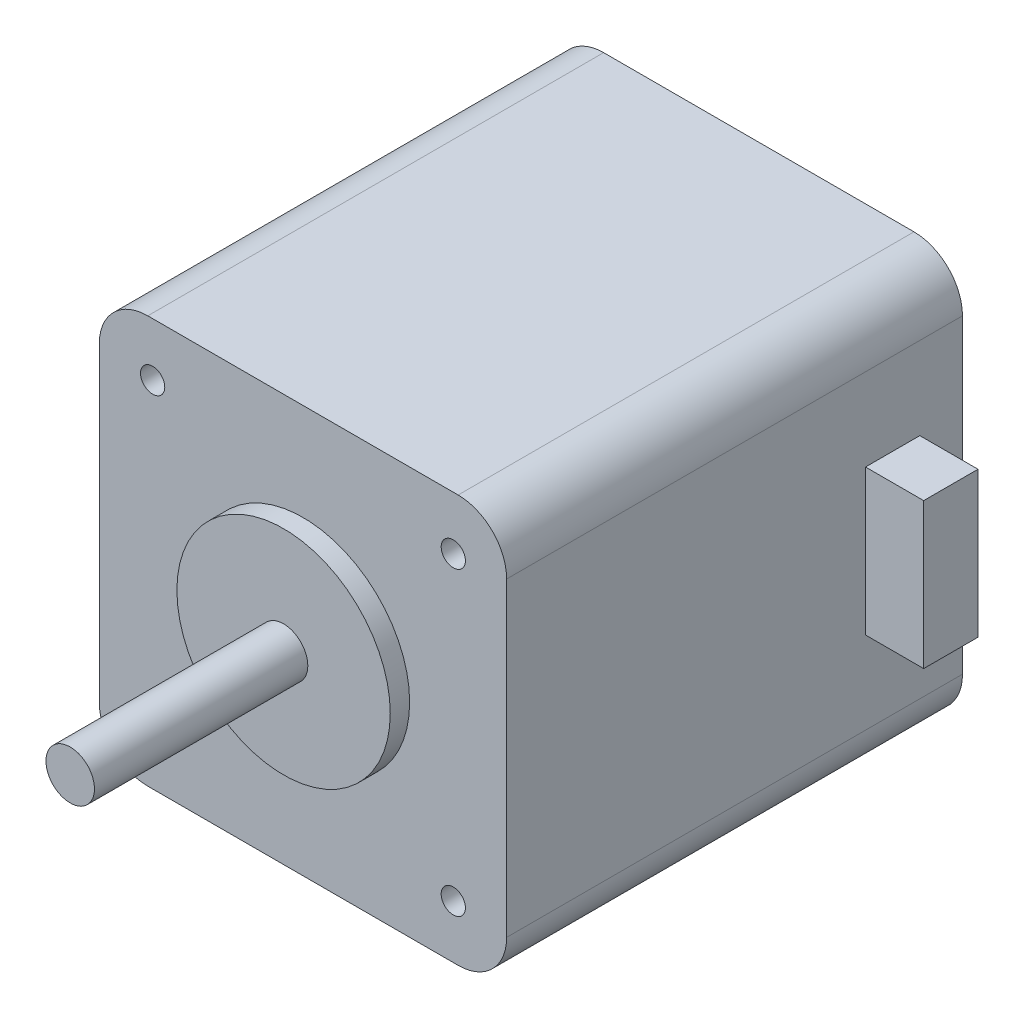
SolidWorks part; units mm, degrees
ref_plane "Front Plane" through (0, 0, 0) normal (0, 0, 1) x (1, 0, 0)
ref_plane "Top Plane" through (0, 0, 0) normal (0, 1, 0) x (1, 0, 0)
ref_plane "Right Plane" through (0, 0, 0) normal (1, 0, 0) x (0, 0, -1)
sketch "Sketch1" plane through (0, 0, 0) normal (0, 0, 1) x (1, 0, 0)
  line L1 (-21, 21) -> (21, 21)
  line L2 (-21, 21) -> (-21, -21)
  line L3 (-21, -21) -> (21, -21)
  line L4 (21, 21) -> (21, -21)
  line L5 (-21, 21) -> (21, -21) construction
  line L6 (-21, -21) -> (21, 21) construction
  point P0 (0, 0)
  dimension "D1" = 42
extrude "Boss-Extrude1" add sketch "Sketch1" along normal blind 47 contours L2 L1 L4 L3
sketch "Sketch2" plane through (0, 0, 47) normal (0, 0, 1) x (1, 0, 0)
  circle A0 centre (0, 0) radius 11
  circle A1 centre (0, 0) radius 2.5
  dimension "D1" = 22
  dimension "D2" = 5
extrude "Boss-Extrude4" add sketch "Sketch2" along normal blind 24 contours A1
extrude "Boss-Extrude5" add sketch "Sketch2<5>" along normal blind 2
sketch "Sketch2<5>" plane through (0, 0, 47) normal (0, 0, 1) x (1, 0, 0) same geometry as "Sketch2"
hole_wizard "M3 Tapped Hole3" positions "3DSketch4" profile "Sketch12" tap size "M3" standard "ISO"
sketch3d "3DSketch4"
  line L0 (-21, 21, 47) -> (-21, -21, 47) construction
  line L1 (-21, 21, 47) -> (21, 21, 47) construction
  point P0 (-15.5, 15.5, 47)
  dimension "D1" = 5.5
  dimension "D2" = 5.5
sketch "Sketch12" plane through (-15.5, 15.5, 47) normal (1, 0, 0) x (0, -1, 0)
  line L0 (0, 0) -> (0, 6.7511)
  line L1 (0, 6.7511) -> (1.25, 6)
  line L2 (1.25, 6) -> (1.25, 0)
  line L5 (1.25, 0) -> (0, 0)
  line L10 (0, 6.7511) -> (-1.25, 6) construction
  line L11 (0, -6.35) -> (0, 107.95) construction
  dimension "Tap Drill Dia." = 2.5
  dimension "Tap Drill Depth" = 6
  dimension "Drill Angle" = 118
cosmetic thread "Hole Thread9" parameters "D1"=4.5, "D2"=3
pattern_circular "CirPattern1" count 4 every 90 about axis through (0, 0, 49) along (0, 0, 1) of "M3 Tapped Hole3"
cosmetic thread "Hole Thread10" parameters "D1"=4.5, "D2"=3
cosmetic thread "Hole Thread11" parameters "D1"=4.5, "D2"=3
cosmetic thread "Hole Thread12" parameters "D1"=4.5, "D2"=3
fillet "Fillet1" radius 5 4 edges at (-21, -21, 23.5) (-21, 21, 23.5) (21, -21, 23.5) (21, 21, 23.5)
sketch "Sketch14" plane through (21, 0, 0) normal (1, 0, 0) x (0, 0, -1)
  line L0 (-10, 7.5) -> (-10, -7.5)
  line L1 (-10, -7.5) -> (-4.4, -7.5)
  line L2 (-4.4, -7.5) -> (-4.4, 7.5)
  line L3 (-4.4, 7.5) -> (-10, 7.5)
  line L4 (0, 16) -> (0, -16) construction
  point P6 (-4.4, 0)
  dimension "D1" = 10
  dimension "D2" = 5.6
  dimension "D3" = 15
extrude "Boss-Extrude6" add sketch "Sketch14" along normal blind 6
